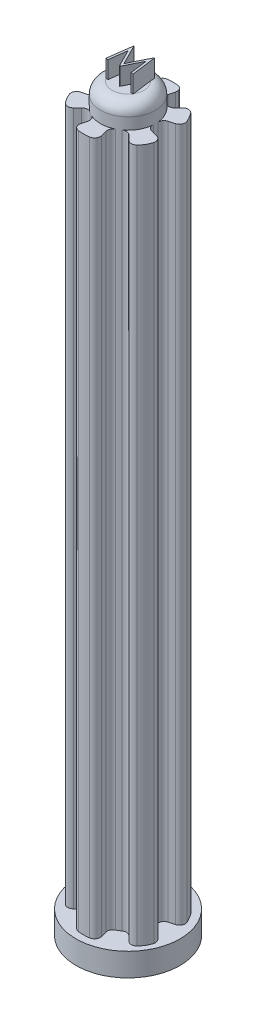
SolidWorks part; units mm, degrees
ref_plane "Front Plane" through (0, 0, 0) normal (0, 0, 1) x (1, 0, 0)
ref_plane "Top Plane" through (0, 0, 0) normal (0, 1, 0) x (1, 0, 0)
ref_plane "Right Plane" through (0, 0, 0) normal (1, 0, 0) x (0, 0, -1)
sketch "Sketch2" plane through (0, 0, 0) normal (0, 1, 0) x (1, 0, 0)
  line L0 (0, 0) -> (0.0739, 0)
  line L2 (2.3008, -0.5891) -> (3.7752, -0.9786)
  line L3 (0.0739, 0) -> (0.1042, -0.0303)
  line L4 (0, 0) -> (0.0858, -0.0446)
  line L5 (1.6802, 1.6786) -> (2.7413, 2.7388)
  line L6 (-1.6794, 1.6794) -> (-2.74, 2.74)
  line L8 (0.6147, 2.2941) -> (1.0029, 3.743)
  line L9 (-0.6147, 2.2941) -> (-1.0029, 3.743)
  line L10 (2.2941, 0.6147) -> (3.743, 1.0029)
  line L11 (0, 0) -> (0.1042, -0.0303)
  line L12 (-2.2941, 0.6147) -> (-3.743, 1.0029)
  line L13 (0.0739, 0) -> (0.0858, -0.0446)
  line L14 (-0.6147, -2.2941) -> (-1.0029, -3.743)
  line L15 (-2.2941, -0.6147) -> (-3.743, -1.0029)
  line L16 (-1.6794, -1.6794) -> (-2.74, -2.74)
  line L17 (0.6814, -2.2752) -> (1.0684, -3.7248)
  line L18 (1.7145, -1.6435) -> (2.7672, -2.6981)
  arc A0 (-2.2941, 0.6147) -> (-2.2941, -0.6147) centre (0, 0) ccw
  arc A1 (-2.74, 2.74) -> (-3.743, 1.0029) centre (0, 0) ccw
  arc A2 (1.0029, 3.743) -> (-1.0029, 3.743) centre (0, 0) ccw
  arc A3 (3.743, 1.0029) -> (2.7413, 2.7388) centre (0, 0) ccw
  arc A5 (-1.0029, -3.743) -> (1.0684, -3.7248) centre (0, 0) ccw
  arc A6 (-3.743, -1.0029) -> (-2.74, -2.74) centre (0, 0) ccw
  arc A7 (-2.74, 2.74) -> (-3.743, 1.0029) centre (0, 0) ccw
  arc A8 (1.0029, 3.743) -> (-1.0029, 3.743) centre (0, 0) ccw
  arc A9 (3.743, 1.0029) -> (2.7413, 2.7388) centre (0, 0) ccw
  arc A10 (-3.743, -1.0029) -> (-2.74, -2.74) centre (0, 0) ccw
  arc A11 (-1.0029, -3.743) -> (1.0684, -3.7248) centre (0, 0) ccw
  arc A12 (2.7672, -2.6981) -> (3.7752, -0.9786) centre (1.7753, -0.9614) ccw
  arc A13 (-0.6147, 2.2941) -> (-1.6794, 1.6794) centre (0, 0) ccw
  arc A14 (1.6802, 1.6786) -> (0.6147, 2.2941) centre (0, 0) ccw
  arc A15 (2.3008, -0.5891) -> (2.2941, 0.6147) centre (0, 0) ccw
  arc A16 (0.6814, -2.2752) -> (1.7145, -1.6435) centre (0, 0) ccw
  arc A17 (-1.6794, -1.6794) -> (-0.6147, -2.2941) centre (0, 0) ccw
  dimension "D1" = 3.875
  dimension "D2" = 2.375
extrude "Boss-Extrude1" add sketch "Sketch2" along normal blind 60 contours L16 A17 L14 A5 L17 A16 L18 A12 L2 A15 L10 A3 L5 A14 L8 A2 L9 A13 L6 A1 L12 A0 L15 A6 L11 L13 L4 L0 L3 region at (0.0225, 0, 0.0171)
sketch "Sketch3" plane through (0, 0, 0) normal (0, -1, 0) x (1, 0, 0)
  circle A0 centre (0, 0) radius 4.5
  dimension "D1" = 9
extrude "Boss-Extrude2" add sketch "Sketch3" along normal blind 2
sketch "Sketch4" plane through (0, 60, 0) normal (0, 1, 0) x (1, 0, 0)
  circle A0 centre (0, 0) radius 2.375
  dimension "D1" = 4.75
extrude "Boss-Extrude3" add sketch "Sketch4" along normal blind 2
fillet "Fillet1" radius 0.5 24 edges at (-2.74, 30, -2.74) (-1.6794, 30, -1.6794) (-0.6147, 30, -2.2941) (-1.0029, 30, -3.743) (1.0029, 30, -3.743) (0.6147, 30, -2.2941) (1.6802, 30, -1.6786) (2.7413, 30, -2.7388) (3.743, 30, -1.0029) (2.2941, 30, -0.6147) (2.3008, 30, 0.5891) (3.7752, 30, 0.9786) (2.7672, 30, 2.6981) (1.7145, 30, 1.6435) (0.6814, 30, 2.2752) (-1.6794, 30, 1.6794) (-2.2941, 30, 0.6147) (-2.2941, 30, -0.6147) (-0.6147, 30, 2.2941) (-3.743, 30, -1.0029) (-3.743, 30, 1.0029) (-2.74, 30, 2.74) (-1.0029, 30, 3.743) (1.0684, 30, 3.7248)
sketch "Sketch5" plane through (0, 62, 0) normal (0, 1, 0) x (1, 0, 0)
  text T0 "M" font "Century Gothic" height in points 8
sketch "Sketch6" plane through (0, -2, 0) normal (0, -1, 0) x (1, 0, 0)
  circle A0 centre (0, 0) radius 1
  dimension "D1" = 2
extrude "Cut-Extrude4" cut sketch "Sketch6" against normal blind 0.5 draft 50
extrude "Boss-Extrude4" add sketch "Sketch5" along normal blind 1.5
fillet "Fillet2" radius 1 1 edges at (0, 62, 2.375)
